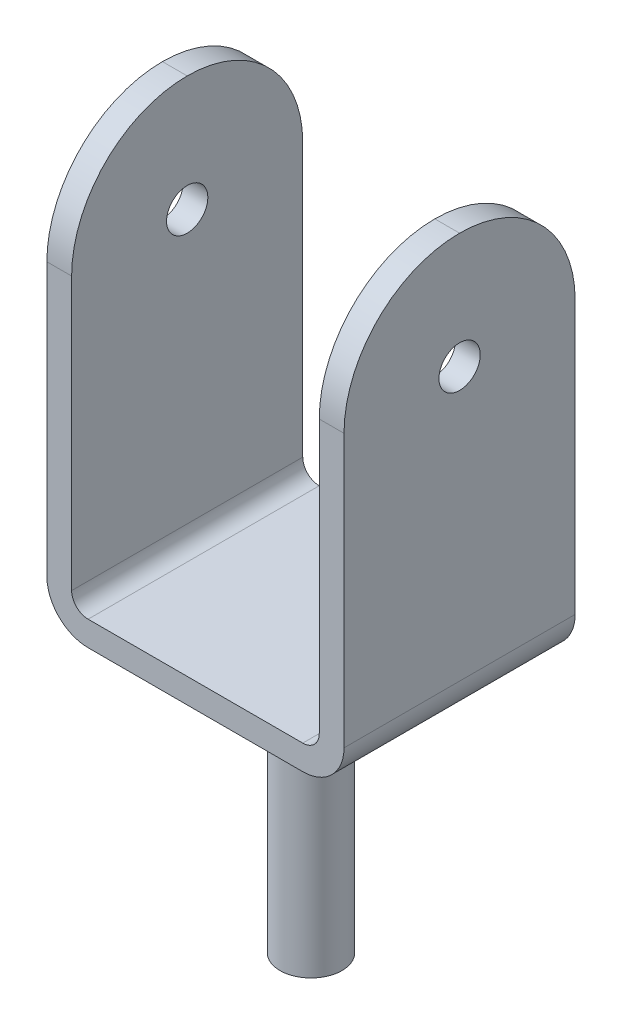
SolidWorks part; units mm, degrees
ref_plane "Front Plane" through (0, 0, 0) normal (0, 0, 1) x (1, 0, 0)
ref_plane "Top Plane" through (0, 0, 0) normal (0, 1, 0) x (1, 0, 0)
ref_plane "Right Plane" through (0, 0, 0) normal (1, 0, 0) x (0, 0, -1)
sketch "Sketch1" plane through (0, 0, 0) normal (0, 0, 1) x (1, 0, 0)
  line L0 (-906.086, 0) -> (838.5294, 0) construction
  line L1 (0, 652.7473) -> (0, -569.6703) construction
  line L2 (-130, 41.5385) -> (130, 41.5385)
  line L3 (150, 61.5385) -> (150, 531.5385)
  line L4 (-150, 531.5385) -> (-150, 61.5385)
  line L5 (-180, 531.5385) -> (-180, 61.5385)
  line L6 (-130, 11.5385) -> (130, 11.5385)
  line L7 (180, 61.5385) -> (180, 531.5385)
  line L8 (-180, 531.5385) -> (-150, 531.5385)
  line L9 (150, 531.5385) -> (180, 531.5385)
  arc A0 (130, 41.5385) -> (150, 61.5385) centre (130, 61.5385) ccw
  arc A1 (-130, 41.5385) -> (-150, 61.5385) centre (-130, 61.5385) cw
  arc A2 (-130, 11.5385) -> (-180, 61.5385) centre (-130, 61.5385) cw
  arc A3 (130, 11.5385) -> (180, 61.5385) centre (130, 61.5385) ccw
  dimension "D2" = 20
  dimension "D1" = 360
  dimension "D4" = 520
  dimension "D5" = 180
  dimension "D3" = 30
extrude "Boss-Extrude1" add sketch "Sketch1" along normal mid plane 280
sketch "Sketch6" plane through (0, 11.5385, 0) normal (0, -1, 0) x (1, 0, 0)
  line L0 (0, 68.7923) -> (0, -60.6305) construction
  line L1 (-93.8607, 0) -> (81.618, 0) construction
  circle A0 centre (0, 0) radius 37.5
  dimension "D1" = 75
extrude "Boss-Extrude3" add sketch "Sketch6" along normal blind 325
fillet "Fillet1" radius 140 4 edges at (-165, 531.5385, -140) (-165, 531.5385, 140) (165, 531.5385, 140) (165, 531.5385, -140)
sketch "Sketch8" plane through (180, 0, 0) normal (1, 0, 0) x (0, 0, -1)
  line L0 (0, 558.8387) -> (0, 91.3298) construction
  line L1 (-140, 391.5385) -> (171.7741, 391.5385) construction
  circle A0 centre (0, 391.5385) radius 25
  dimension "D1" = 50
extrude "Cut-Extrude3" cut sketch "Sketch8" against normal through all
